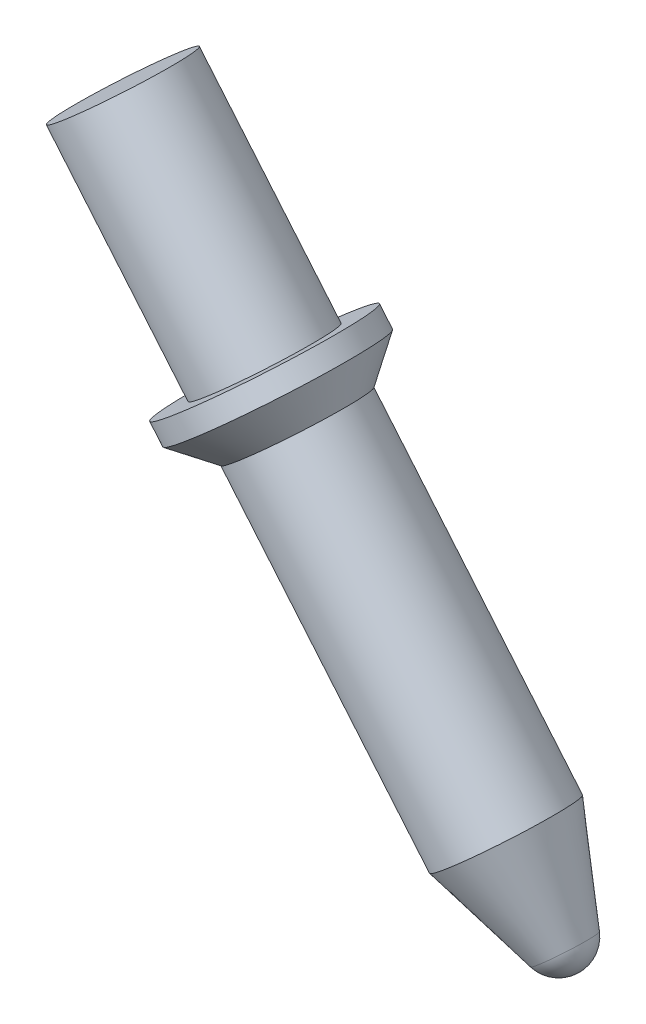
SolidWorks part; units mm, degrees
note: '?' marks a value the reader was unsure of.
ref_plane "Front Plane" through (0, 0, 0) normal (0, 0, 1) x (1, 0, 0)
ref_plane "Top Plane" through (0, 0, 0) normal (0, 1, 0) x (1, 0, 0)
ref_plane "Right Plane" through (0, 0, 0) normal (1, 0, 0) x (0, 0, -1)
sketch "Sketch1" plane through (0, 0, 0) normal (0, 0, 1) x (1, 0, 0)
  line L1 (8.1634, -9.7288) -> (49.5107, 24.9657)
  line L2 (49.5107, 24.9657) -> (38.4897, 38.1)
  line L3 (38.4897, 38.1) -> (-38.4897, 38.1)
  line L4 (0, 34.4769) -> (0, 78.412) construction
  line L5 (-49.5107, 24.9657) -> (-38.4897, 38.1)
  line L6 (-8.1634, -9.7288) -> (-49.5107, 24.9657)
  circle A0 centre (0, 0) radius 5.7531
  arc A1 (-8.1634, -9.7288) -> (8.1634, -9.7288) centre (0, 0) ccw
  point P10 (-22.7565, 2.5163)
  point P11 (32.4853, 10.6797)
  point P13 (-42.2141, 18.8431)
  dimension "D4" = 50.8
  dimension "D5" = 11.5062
  dimension "D2" = 12.7
  dimension "D1" = 53.975
  dimension "D3" = 40
  dimension "D6" = 9.525
  dimension "D7" = 53.975
  dimension "D8" = 25.4
  dimension "D9" = 22.225
  dimension "D10" = 64.9706
extrude "Boss-Extrude1" [suppressed] add sketch "Sketch1" along normal mid plane 15.875
ref_axis "Axis1" through (0, 131.1151, 0) along (0, -1, 0)?
fillet "Fillet1" [suppressed] radius 9.525
hole_wizard "1/4-28 Tapped Hole1" [suppressed] positions "Sketch4" profile "Sketch3" tap size "1/4-28" standard "ANSI Inch"
sketch "Sketch4" [suppressed] plane through (-8.1634, -9.7288, 0) normal (-0.6428, -0.766, 0) x (-0.766, 0.6428, 0)
  point P0 (19.05, 0)
  point P1 (44.45, 0)
sketch "Sketch3" plane through (-22.7565, 2.5163, 0) normal (0, 0, 1) x (0.766, -0.6428, 0)
  line L0 (0, 0) -> (0, 20.6754)
  line L1 (0, 20.6754) -> (2.7051, 19.05)
  line L2 (2.7051, 19.05) -> (2.7051, 1.1049)
  line L3 (2.7051, 1.1049) -> (3.81, 0)
  line L5 (3.81, 0) -> (0, 0)
  line L6 (-2.7051, 1.1049) -> (-3.81, 0) construction
  line L10 (0, 20.6754) -> (-2.7051, 19.05) construction
  line L11 (0, -6.35) -> (0, 107.95) construction
  dimension "Tap Drill Dia." = 5.4102
  dimension "Tap Drill Depth" = 19.05
  dimension "Near C'Sink Dia." = 7.62
  dimension "Near C'Sink Angle" = 90
  dimension "Drill Angle" = 118
sketch "Sketch5" plane through (0, 0, 0) normal (0, 0, 1) x (1, 0, 0)
  line L0 (0.0276, 49.3613) -> (35.7507, 6.7882)
  line L1 (35.7507, 6.7882) -> (39.4087, 9.8577)
  line L2 (39.4087, 9.8577) -> (23.8982, 28.3423)
  line L3 (23.8982, 28.3423) -> (21.191, 27.9135)
  line L4 (21.191, 27.9135) -> (14.9473, 35.3545)
  line L5 (14.9473, 35.3545) -> (16.1342, 36.3504)
  line L6 (16.1342, 36.3504) -> (3.0727, 51.9165)
  line L7 (0.0276, 49.3613) -> (3.0727, 51.9165)
  line L8 (35.7507, 6.7882) -> (50.4262, -10.7014) construction
  line L9 (8.1634, -9.7288) -> (49.5107, 24.9657) construction
  dimension "D1" = 5.08
  dimension "D2" = 19.05
  dimension "D3" = 30.1752
  dimension "D4" = 7.9502
  dimension "D5" = 4.8514
  dimension "D6" = 9.5504
  dimension "D7" = 59
  dimension "D8" = 20.32
revolve "Cut-Revolve1" [suppressed] cut sketch "Sketch5" angle 360 about L8
sketch "Sketch2" plane through (0, 0, 0) normal (0, 0, 1) x (1, 0, 0)
  line L0 (25.0477, 26.9527) -> (36.1499, 13.7216)
  line L1 (36.1499, 13.7216) -> (37.9789, 15.2563)
  line L2 (37.9789, 15.2563) -> (39.0075, 14.0305)
  line L3 (39.0075, 14.0305) -> (38.7132, 10.6667)
  line L4 (38.7132, 10.6667) -> (55.0593, -8.8137)
  line L5 (55.0593, -8.8137) -> (57.6713, -15.9902)
  line L6 (56.9918, -18.526) -> (21.3994, 23.8914)
  line L7 (21.3994, 23.8914) -> (25.0477, 26.9527)
  line L8 (56.9918, -18.526) -> (55.7676, -17.067) construction
  line L9 (8.1634, -9.7288) -> (49.5107, 24.9657) construction
  arc A0 (57.6713, -15.9902) -> (56.9918, -18.526) centre (55.5208, -16.7729) cw
  dimension "D7" = 2.2885
  dimension "D1" = 45
  dimension "D2" = 9.525
  dimension "D3" = 9.525
  dimension "D4" = 14.3002
  dimension "D5" = 1.6002
  dimension "D6" = 20
  dimension "D8" = 38.1
  dimension "D9" = 17.272
  dimension "D10" = 1.6256
revolve "Revolve1" add sketch "Sketch2" angle 360 about L8
fillet "Fillet2" [suppressed] radius 0.635
